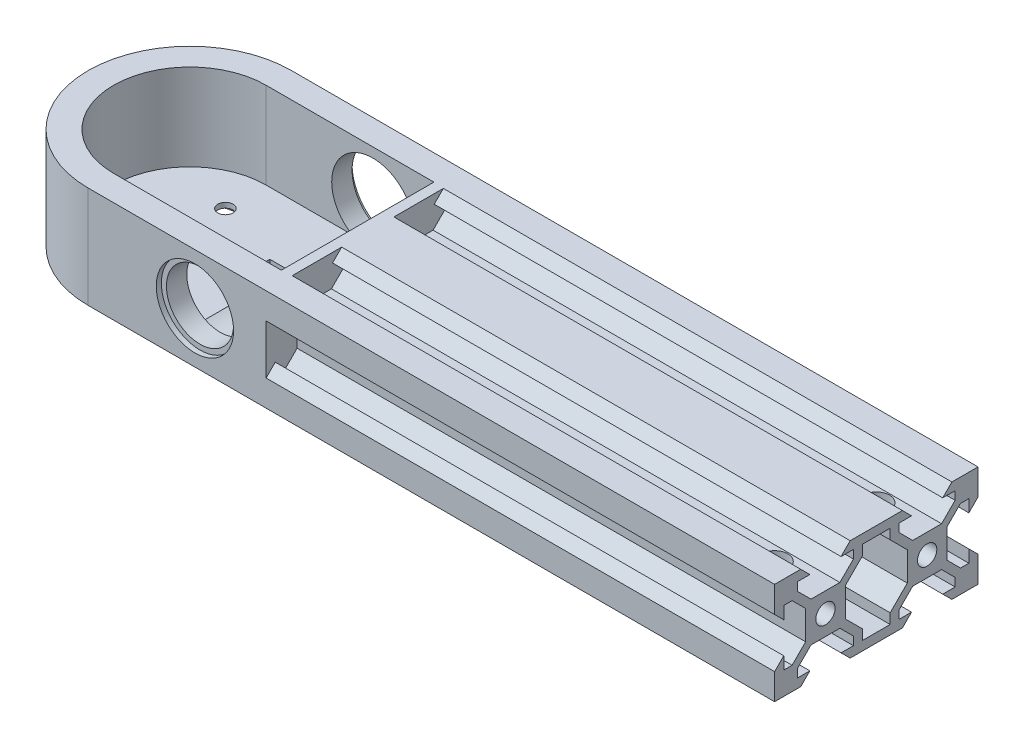
SolidWorks part; units mm, degrees
ref_plane "Front Plane" through (0, 0, 0) normal (0, 0, 1) x (1, 0, 0)
ref_plane "Top Plane" through (0, 0, 0) normal (0, 1, 0) x (1, 0, 0)
ref_plane "Right Plane" through (0, 0, 0) normal (1, 0, 0) x (0, 0, -1)
sketch "Sketch1" plane through (0, 0, 0) normal (0, 1, 0) x (1, 0, 0)
  line L1 (-47.5, -20) -> (47.5, -20)
  line L2 (-47.5, -20) -> (-47.5, 20)
  line L3 (-47.5, 20) -> (47.5, 20)
  line L4 (47.5, -20) -> (47.5, 20)
  line L5 (0, 20) -> (0, -20) construction
  line L6 (-47.5, 0) -> (47.5, 0) construction
  point P0 (0, 0)
  dimension "D1" = 95
  dimension "D2" = 40
extrude "Boss-Extrude1" add sketch "Sketch1" along normal blind 20
sketch "Sketch8" plane through (0, 0, 0) normal (0, -1, 0) x (-1, 0, 0)
  line L0 (52.5, -15) -> (87.5, -15)
  line L1 (47.5, -20) -> (87.5, -20)
  line L2 (47.5, -20) -> (47.5, 20)
  line L3 (47.5, 20) -> (87.5, 20)
  line L5 (52.5, 15) -> (87.5, 15)
  line L6 (52.5, -15) -> (52.5, 15)
  arc A0 (87.5, -20) -> (87.5, 20) centre (87.5, 0) ccw
  arc A1 (87.5, -15) -> (87.5, 15) centre (87.5, 0) ccw
  dimension "D1" = 5
  dimension "D2" = 40
  dimension "D3" = 40
extrude "Boss-Extrude3" add sketch "Sketch8<3>" against normal blind 3 contours L0 A1 L5 L6 region at (-76.0103, 0, 0)
sketch "Sketch8<3>" plane through (0, 0, 0) normal (0, -1, 0) x (-1, 0, 0) same geometry as "Sketch8"
extrude "Boss-Extrude2" add sketch "Sketch8" against normal up to vertex (20 mm away) up to point (-47.5, 20, 20)
sketch "Sketch7" plane through (47.5, 0, 0) normal (1, 0, 0) x (0, 0, -1)
  line L0 (-20, 0) -> (20, 0) construction
  line L1 (-20, 20) -> (20, 20) construction
  line L2 (-20, 20) -> (-20, 0) construction
  line L3 (-20, 0) -> (20, 0) construction
  line L4 (0, 20) -> (0, 0) construction
  line L5 (-7.1593, 13.9) -> (-4.4993, 16.56)
  line L12 (-12.8393, 13.9) -> (-7.1593, 13.9)
  line L14 (-12.8393, 13.9) -> (-15.4993, 16.56)
  line L15 (-4.4993, 16.56) -> (-4.4993, 18.2)
  line L20 (-15.4993, 16.56) -> (-15.4993, 18.2)
  line L21 (-4.4993, 18.2) -> (-6.9343, 18.2)
  line L22 (-13.0643, 18.2) -> (-14.8643, 20)
  line L23 (-15.4993, 18.2) -> (-13.0643, 18.2)
  line L24 (-18.2, 13.0643) -> (-20, 14.8643)
  line L25 (-20, 20) -> (-20, 14.8643)
  line L26 (-6.9343, 18.2) -> (-5.1343, 20)
  line L27 (-18.2, 13.0643) -> (-18.2, 15.4993)
  line L28 (-18.2, 15.4993) -> (-16.56, 15.4993)
  line L29 (-16.56, 15.4993) -> (-13.9, 12.8393)
  line L30 (-14.8643, 20) -> (-20, 20)
  line L31 (-13.9, 12.8393) -> (-13.9, 7.1593)
  line L36 (-6.0987, 12.8393) -> (-6.0987, 7.1593)
  line L37 (-4.4993, 16.56) -> (-7.1593, 13.9) [skipped]
  line L38 (-6.0987, 12.8393) -> (-3.4387, 15.4993) [skipped]
  line L39 (-3.4387, 15.4993) -> (-1.7987, 15.4993) [skipped]
  line L40 (-1.7987, 15.4993) -> (-1.7987, 13.0643) [skipped]
  line L41 (-1.7987, 13.0643) -> (0.0013, 14.8643) [skipped]
  line L42 (0.0013, 14.8643) -> (0.0013, 20) [skipped]
  line L43 (0.0013, 20) -> (-5.1343, 20) [skipped]
  line L44 (-6.9343, 18.2) -> (-5.1343, 20) [skipped]
  line L45 (-6.9343, 18.2) -> (-4.4993, 18.2) [skipped]
  line L46 (-4.4993, 18.2) -> (-4.4993, 16.56) [skipped]
  line L48 (-6.0987, 7.1593) -> (-2.73, 3.7907)
  line L49 (-7.1593, 6.0987) -> (-4.4993, 3.4387)
  line L50 (-4.4993, 3.4387) -> (-4.4993, 1.7987)
  line L51 (-4.4993, 1.7987) -> (-6.9343, 1.7987)
  line L52 (-6.9343, 1.7987) -> (-5.1343, -0.0013)
  line L54 (-5.1343, 20) -> (5.1343, 20)
  line L58 (-2.73, 18.2) -> (2.73, 18.2)
  line L59 (-15.4993, 3.4387) -> (-12.8393, 6.0987)
  line L60 (-13.9, 7.1593) -> (-16.56, 4.4993)
  line L61 (-16.56, 4.4993) -> (-18.2, 4.4993)
  line L62 (-18.2, 4.4993) -> (-18.2, 6.9343)
  line L63 (-18.2, 6.9343) -> (-20, 5.1343)
  line L64 (-20, 5.1343) -> (-20, -0.0013)
  line L65 (-20, -0.0013) -> (-14.8643, -0.0013)
  line L66 (-13.0643, 1.7987) -> (-14.8643, -0.0013)
  line L67 (-13.0643, 1.7987) -> (-15.4993, 1.7987)
  line L68 (-15.4993, 1.7987) -> (-15.4993, 3.4387)
  line L69 (-6.0987, 12.8393) -> (-2.73, 16.208)
  line L70 (-12.8393, 6.0987) -> (-7.1593, 6.0987)
  line L71 (-3.4387, 4.4993) -> (-6.0987, 7.1593) [skipped]
  line L72 (-1.7987, 4.4993) -> (-3.4387, 4.4993) [skipped]
  line L73 (-1.7987, 6.9343) -> (0.0013, 5.1343) [skipped]
  line L74 (-1.7987, 6.9343) -> (-1.7987, 4.4993) [skipped]
  line L87 (-2.73, 16.208) -> (-2.73, 18.2)
  line L88 (-2.73, 3.7907) -> (-2.73, 1.7987)
  line L113 (0.0013, -0.0013) -> (0.0013, 5.1343) [skipped]
  line L114 (-5.1343, -0.0013) -> (0.0013, -0.0013) [skipped]
  line L115 (-2.73, 1.7987) -> (2.73, 1.7987)
  line L116 (-5.1343, -0.0013) -> (0, 0)
  line L117 (20, 20) -> (20, 0) construction
  line L118 (5.1343, -0.0013) -> (0, 0)
  line L119 (2.73, 3.7907) -> (2.73, 1.7987)
  line L120 (2.73, 16.208) -> (2.73, 18.2)
  line L121 (12.8393, 6.0987) -> (7.1593, 6.0987)
  line L122 (6.0987, 12.8393) -> (2.73, 16.208)
  line L123 (15.4993, 1.7987) -> (15.4993, 3.4387)
  line L124 (13.0643, 1.7987) -> (15.4993, 1.7987)
  line L125 (13.0643, 1.7987) -> (14.8643, -0.0013)
  line L126 (20, -0.0013) -> (14.8643, -0.0013)
  line L127 (20, 5.1343) -> (20, -0.0013)
  line L128 (18.2, 6.9343) -> (20, 5.1343)
  line L129 (18.2, 4.4993) -> (18.2, 6.9343)
  line L130 (16.56, 4.4993) -> (18.2, 4.4993)
  line L131 (13.9, 7.1593) -> (16.56, 4.4993)
  line L132 (15.4993, 3.4387) -> (12.8393, 6.0987)
  line L133 (6.9343, 1.7987) -> (5.1343, -0.0013)
  line L134 (4.4993, 1.7987) -> (6.9343, 1.7987)
  line L135 (4.4993, 3.4387) -> (4.4993, 1.7987)
  line L136 (7.1593, 6.0987) -> (4.4993, 3.4387)
  line L137 (6.0987, 7.1593) -> (2.73, 3.7907)
  line L138 (6.0987, 12.8393) -> (6.0987, 7.1593)
  line L139 (13.9, 12.8393) -> (13.9, 7.1593)
  line L140 (14.8643, 20) -> (20, 20)
  line L141 (16.56, 15.4993) -> (13.9, 12.8393)
  line L142 (18.2, 15.4993) -> (16.56, 15.4993)
  line L143 (18.2, 13.0643) -> (18.2, 15.4993)
  line L144 (6.9343, 18.2) -> (5.1343, 20)
  line L145 (20, 20) -> (20, 14.8643)
  line L146 (18.2, 13.0643) -> (20, 14.8643)
  line L147 (15.4993, 18.2) -> (13.0643, 18.2)
  line L148 (13.0643, 18.2) -> (14.8643, 20)
  line L149 (4.4993, 18.2) -> (6.9343, 18.2)
  line L150 (15.4993, 16.56) -> (15.4993, 18.2)
  line L151 (4.4993, 16.56) -> (4.4993, 18.2)
  line L152 (12.8393, 13.9) -> (15.4993, 16.56)
  line L153 (12.8393, 13.9) -> (7.1593, 13.9)
  line L154 (7.1593, 13.9) -> (4.4993, 16.56)
  circle A0 centre (-10, 10) radius 1.9
  circle A1 centre (10, 10) radius 1.9
  point P36 (0, 1.7987)
  point P81 (-9.9993, 9.9993)
  point P84 (0, 18.2)
  point P103 (9.9993, 9.9993)
  line M26 (-20, 0) -> (20, 0)
  line M27 (20, 0) -> (20, 20)
  line M28 (20, 20) -> (-20, 20)
  line M29 (-20, 20) -> (-20, 0)
  dimension "D1" = 4.3
  dimension "D2" = 6.13
  dimension "D3" = 11
  dimension "D4" = 4.3
  dimension "D5" = 4.3
  dimension "D6" = 1.8
  dimension "D7" = 1.8
  dimension "D8" = 1.5
  dimension "D9" = 1.5
  dimension "D12" = 1.5
  dimension "D13" = 5.68
  dimension "D10" = 4
extrude "Cut-Extrude5" cut sketch "Sketch7" along direction (1, 0, 0) on the side against the normal up to vertex (100 mm away) contours L63 L62 L61 L60 L31 L29 L28 L27 L24 M29 | L21 L26 L22 L23 L20 L14 L12 L5 L15 M28 | L70 L59 L68 L67 L66 L52 L51 L50 L49 M26 | L154 L153 L152 L150 L147 L148 L144 L149 L151 M28 | L121 L136 L135 L134 L133 L125 L124 L123 L132 M26 | L146 L143 L142 L141 L139 L131 L130 L129 L128 M27 | L138 L122 L120 L58 L87 L69 L36 L48 L88 L115 L119 L137 | A0 | A1 region at (47.5, 17.0307, 9.9993) region at (47.5, 9.9993, -0.2124) region at (47.5, 16.2362, 1.326) region at (47.5, 17.0307, -9.9993) region at (47.5, 9.9993, 17.0307) region at (47.5, 9.9993, -17.0307) region at (47.5, 2.9687, 9.9993) region at (47.5, 3.7625, 1.326) region at (47.5, 2.9687, -9.9993) region at (47.5, 10, 10) region at (47.5, 10, -10) up to point (-52.5, 20, 15)
sketch "Sketch9" plane through (-52.5, 0, 0) normal (-1, 0, 0) x (0, 0, 1)
  line L0 (-15, 20) -> (-2.73, 20)
  line L1 (-5.1343, 20) -> (5.1343, 20) construction
  line L3 (-2.73, 16.208) -> (-6.0987, 12.8393)
  line L4 (-6.0987, 12.8393) -> (-6.0987, 7.1593)
  line L5 (-6.0987, 7.1593) -> (-2.73, 3.7907)
  line L6 (-2.73, 3.7907) -> (-2.73, 3)
  line L7 (15, 3) -> (-15, 3) construction
  line L8 (-2.73, 3.7907) -> (-2.73, 1.7987) construction
  line L9 (-2.73, 3) -> (-15, 3)
  line L10 (-15, 3) -> (-15, 20)
  line L11 (15, 20) -> (2.73, 20)
  line L14 (2.73, 16.208) -> (6.0987, 12.8393)
  line L15 (6.0987, 12.8393) -> (6.0987, 7.1593)
  line L16 (6.0987, 7.1593) -> (2.73, 3.7907)
  line L17 (2.73, 3.7907) -> (2.73, 3)
  line L18 (2.73, 3.7907) -> (2.73, 1.7987) construction
  line L19 (2.73, 3) -> (15, 3)
  line L20 (15, 3) -> (15, 20)
  line L21 (2.73, 16.208) -> (2.73, 18.2)
  line L22 (2.73, 18.2) -> (-2.73, 18.2)
  line L23 (-2.73, 18.2) -> (-2.73, 16.208)
  line L24 (2.73, 20) -> (-2.73, 20)
extrude "Boss-Extrude4" add sketch "Sketch9" along normal blind 2
sketch "Sketch10" plane through (0, 0, 0) normal (0, -1, 0) x (-1, 0, 0)
  circle A0 centre (87.5, 0) radius 10.5
  arc A1 (87.5, -20) -> (87.5, 20) centre (87.5, 0) ccw construction
  point P5 (107.5, 0)
  dimension "D1" = 21
  dimension "D2" = 20
  dimension "D3" = 20
extrude "Cut-Extrude6" cut sketch "Sketch10" against normal blind 2
sketch "Sketch12" plane through (0, 2, 0) normal (0, -1, 0) x (-1, 0, 0)
  line L0 (94.5, 0) -> (80.5, 0) construction
  line L1 (87.5, 7) -> (87.5, -7) construction
  circle A0 centre (87.5, 0) radius 2
  circle A1 centre (87.5, -7) radius 1.5
  circle A2 centre (80.5, 0) radius 1.5
  circle A3 centre (87.5, 7) radius 1.5
  circle A4 centre (94.5, 0) radius 1.5
  circle A5 centre (87.5, 0) radius 10.5 construction
  point P7 (87.5, 0)
  point P10 (87.5, 0)
  dimension "D1" = 4
  dimension "D2" = 3
  dimension "D5" = 8.5
  dimension "D3" = 14
  dimension "D4" = 14
extrude "Cut-Extrude7" cut sketch "Sketch12" against normal up to next
sketch "Sketch13" plane through (0, 0, 20) normal (0, 0, 1) x (1, 0, 0)
  line L0 (-87.5, 20) -> (-13, 20) construction
  line L2 (-87.5, 20) -> (47.5, 20) construction
  line L3 (-52.5, 14.8643) -> (-52.5, 5.1343) construction
  circle A0 centre (-66.5, 9.9993) radius 7.6
  point P4 (0, 0)
  point P7 (0, 0)
  point P12 (-52.5, 9.9993)
  dimension "D2" = 15.2
  dimension "D1" = 12
extrude "Cut-Extrude9" cut sketch "Sketch13" against normal blind 1
sketch "Sketch15" plane through (0, 0, 19) normal (0, 0, 1) x (1, 0, 0)
  circle A0 centre (-66.5, 9.9993) radius 6.6
  dimension "D1" = 13.2
extrude "Cut-Extrude10" cut sketch "Sketch15" against normal up to next
sketch "Sketch16" plane through (0, 13.9, 0) normal (0, 1, 0) x (1, 0, 0)
  line L2 (47.5, 12.8393) -> (47.5, 7.1593) construction
  line L3 (47.5, -12.8393) -> (47.5, -7.1593) construction
  circle A0 centre (37.5, -9.9993) radius 2.6
  circle A1 centre (37.5, 9.9993) radius 2.6
  dimension "D1" = 5.2
  dimension "D2" = 5.2
  dimension "D3" = 10
  dimension "D4" = 10
extrude "Cut-Extrude11" cut sketch "Sketch16" against normal through all
sketch "Sketch18" plane through (0, 0, -20) normal (0, 0, -1) x (-1, 0, 0)
  circle A0 centre (66.5, 9.9993) radius 9.1
  dimension "D1" = 18.2
extrude "Cut-Extrude12" cut sketch "Sketch18" against normal blind 1
sketch "Sketch19" plane through (0, 0, -19) normal (0, 0, -1) x (-1, 0, 0)
  circle A0 centre (66.5, 9.9993) radius 8.1
  dimension "D1" = 16.2
extrude "Cut-Extrude15" cut sketch "Sketch19" against normal up to surface (34 mm away) up to face at (-59.9, 9.9993, 15)
sketch "Sketch20" plane through (-52.5, 0, 0) normal (1, 0, 0) x (0, 0, -1)
  line L1 (-2.73, 3) -> (2.73, 3)
  line L2 (-2.73, 3) -> (-2.73, 1.7987)
  line L3 (-2.73, 1.7987) -> (2.73, 1.7987)
  line L4 (2.73, 3) -> (2.73, 1.7987)
extrude "Cut-Extrude16" cut sketch "Sketch20" against normal blind 22
